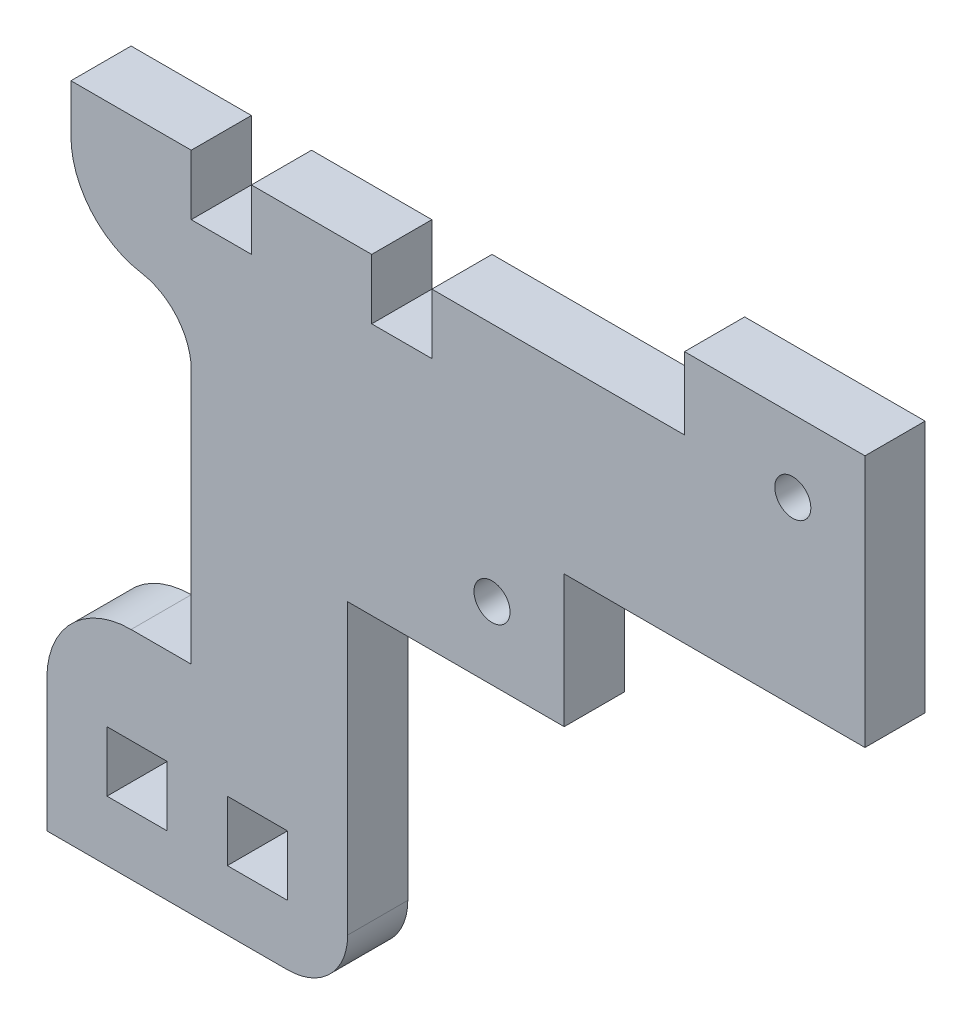
SolidWorks part; units mm, degrees
ref_plane "Plan de face" through (0, 0, 0) normal (0, 0, 1) x (1, 0, 0)
ref_plane "Plan de dessus" through (0, 0, 0) normal (0, 1, 0) x (1, 0, 0)
ref_plane "Plan de droite" through (0, 0, 0) normal (1, 0, 0) x (0, 0, -1)
sketch "Esquisse1" plane through (0, 0, 0) normal (0, 0, 1) x (1, 0, 0)
  line L0 (25, 19) -> (43, 19)
  line L1 (5, 0) -> (10, 0)
  line L2 (0, 0) -> (0, 8)
  line L3 (12, 40) -> (17, 40)
  line L4 (68, 30) -> (68, 51)
  line L5 (27, 40) -> (32, 40)
  line L6 (2, 40) -> (2, 45)
  line L7 (2, 45) -> (12, 45)
  line L8 (12, 40) -> (12, 45)
  line L9 (15, 0) -> (20, 0)
  line L10 (17, 40) -> (17, 45)
  line L11 (17, 45) -> (27, 45)
  line L12 (27, 40) -> (27, 45)
  line L13 (15, 0) -> (15, -5)
  line L14 (10, -5) -> (5, -5)
  line L15 (10, 0) -> (10, -5)
  line L16 (5, 0) -> (5, -5)
  line L18 (0, 0) -> (0, -5.81)
  line L19 (2, 34) -> (2, 40)
  line L20 (0, 8) -> (12, 8)
  line L22 (2, 34) -> (12, 34)
  line L23 (12, 8) -> (12, 34)
  line L24 (20, 0) -> (20, -5)
  line L25 (43, 19) -> (43, 30)
  line L26 (43, 30) -> (68, 30)
  line L27 (53, 45) -> (53, 51)
  line L28 (53, 51) -> (68, 51)
  line L29 (32, 40) -> (32, 45)
  line L30 (25, 19) -> (25, -4.929)
  line L31 (20, -5) -> (15, -5)
  line L32 (25, -4.929) -> (25, -10)
  line L33 (25, -10) -> (0, -10)
  line L34 (0, -5.81) -> (0, -10)
  line L35 (32, 45) -> (53, 45)
  circle A0 centre (62, 45) radius 1.5
  circle A1 centre (37, 25) radius 1.5
  circle A2 centre (37, 25) radius 1.5 construction
  circle A3 centre (62, 45) radius 1.5 construction
  dimension "D9" = 3
  dimension "D11" = 6
  dimension "D14" = 6
  dimension "D12" = 6
  dimension "D3" = 10
  dimension "D4" = 5
  dimension "D5" = 5
  dimension "D6" = 10
  dimension "D7" = 8
  dimension "D8" = 26
  dimension "D10" = 5
  dimension "D16" = 6
  dimension "D17" = 15
  dimension "D18" = 40
  dimension "D19" = 2
  dimension "D20" = 5
  dimension "D21" = 5
  dimension "D22" = 5
  dimension "D23" = 5
  dimension "D24" = 25
extrude "Boss.-Extru.1" add sketch "Esquisse1" along normal blind 5
fillet "Congé1" radius 7 2 edges at (0, 8, 2.5) (2, 34, 2.5)
fillet "Congé2" radius 5 1 edges at (12, 34, 2.5)
fillet "Congé3" radius 5 1 edges at (25, -10, 2.5)
